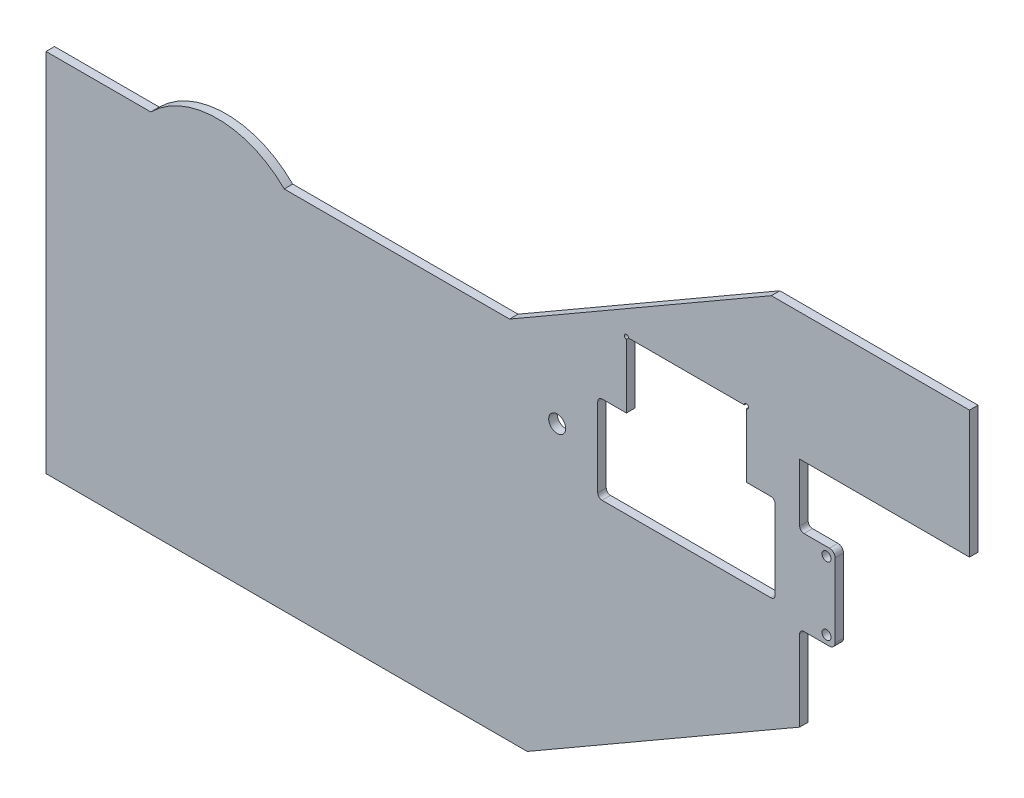
SolidWorks part; units mm, degrees
material "Thornel Mat VMA"
ref_plane "Front Plane" through (0, 0, 0) normal (0, 0, 1) x (1, 0, 0)
ref_plane "Top Plane" through (0, 0, 0) normal (0, 1, 0) x (1, 0, 0)
ref_plane "Right Plane" through (0, 0, 0) normal (1, 0, 0) x (0, 0, -1)
sketch "Sketch1" plane through (0, 0, 0) normal (0, 0, 1) x (1, 0, 0)
  line L1 (-20.4587, 47.6) -> (-183.6375, 47.6)
  line L2 (-20.4587, 47.6) -> (-20.4587, -36.0143)
  line L3 (-20.4587, -36.0143) -> (-183.6375, -36.0143)
  line L4 (-183.6375, 47.6) -> (-183.6375, -36.0143)
extrude "Boss-Extrude1" add sketch "Sketch1" along normal blind 3
sketch "Sketch2" plane through (0, 0, 3) normal (0, 0, 1) x (1, 0, 0)
  circle A0 centre (-24.2887, 24) radius 3
  dimension "D1" = 6
extrude "Cut-Extrude1" cut sketch "Sketch2" against normal blind 70
sketch "Sketch3" plane through (0, 0, 3) normal (0, 0, 1) x (1, 0, 0)
  line L4 (-20.4587, -36.0143) -> (-20.4587, 47.6)
  line L5 (-20.4587, 47.6) -> (-183.6375, 47.6)
  line L6 (-183.6375, 47.6) -> (-183.6375, -36.0143)
  line L7 (-183.6375, -36.0143) -> (-20.4587, -36.0143)
  line L8 (-20.4587, -36.0143) -> (-20.4587, 47.6)
  line L9 (-20.4587, 47.6) -> (-41.1202, 47.6)
  line L10 (-183.6375, 47.6) -> (-183.6375, -36.0143)
  line L11 (-183.6375, -36.0143) -> (-20.4587, -36.0143)
  line L13 (51.3713, 101) -> (-41.1202, 47.6)
  line L14 (-41.1202, 47.6) -> (-120.7247, 47.6)
  line L15 (-204.873, 47.6) -> (-204.873, -81.5667)
  line L16 (-204.873, -81.5667) -> (-34.873, -81.5667)
  line L17 (-34.873, -81.5667) -> (61.3713, -26)
  line L18 (61.3713, -26) -> (61.3713, 2.5)
  line L19 (62.8713, 4) -> (71.8713, 4)
  line L20 (73.8713, 6) -> (73.8713, 32)
  line L21 (71.8713, 34) -> (62.8713, 34)
  line L22 (61.3713, 35.5) -> (61.3713, 56)
  line L23 (61.3713, 56) -> (121.3713, 56)
  line L24 (121.3713, 56) -> (121.3713, 101)
  line L25 (121.3713, 101) -> (51.3713, 101)
  line L26 (51.3713, 101) -> (-41.1202, 47.6)
  line L27 (-167.8527, 47.6) -> (-120.7247, 47.6)
  line L28 (-204.873, 47.6) -> (-204.873, -81.5667)
  line L29 (-204.873, -81.5667) -> (-34.873, -81.5667)
  line L30 (-34.873, -81.5667) -> (61.3713, -26)
  line L31 (61.3713, -26) -> (61.3713, 2.5)
  line L32 (62.8713, 4) -> (71.8713, 4)
  line L33 (73.8713, 6) -> (73.8713, 32)
  line L34 (71.8713, 34) -> (62.8713, 34)
  line L35 (61.3713, 35.5) -> (61.3713, 56)
  line L36 (61.3713, 56) -> (121.3713, 56)
  line L37 (121.3713, 56) -> (121.3713, 101)
  line L38 (121.3713, 101) -> (51.3713, 101)
  line L265 (-167.8527, 47.6) -> (-204.873, 47.6)
  line L266 (-183.6375, 47.6) -> (-204.873, 47.6)
  circle A0 centre (70.8713, 31) radius 1.6 construction
  circle A1 centre (70.8713, 7) radius 1.6 construction
  arc A2 (71.8713, 4) -> (73.8713, 6) centre (71.8713, 6) ccw
  arc A3 (73.8713, 32) -> (71.8713, 34) centre (71.8713, 32) ccw
  arc A4 (71.8713, 4) -> (73.8713, 6) centre (71.8713, 6) ccw
  arc A5 (73.8713, 32) -> (71.8713, 34) centre (71.8713, 32) ccw
  circle A6 centre (70.8713, 31) radius 1.6
  circle A7 centre (70.8713, 7) radius 1.6
  arc A38 (62.8713, 4) -> (61.3713, 2.5) centre (62.8713, 2.5) ccw
  arc A39 (62.8713, 4) -> (61.3713, 2.5) centre (62.8713, 2.5) ccw
  arc A40 (61.3713, 35.5) -> (62.8713, 34) centre (62.8713, 35.5) ccw
  arc A41 (61.3713, 35.5) -> (62.8713, 34) centre (62.8713, 35.5) ccw
  arc A60 (-120.7247, 47.6) -> (-167.8527, 47.6) centre (-144.2887, 24) ccw
  arc A61 (-120.7247, 47.6) -> (-167.8527, 47.6) centre (-144.2887, 24) ccw
  dimension "D1" = 0
  dimension "D2" = 0
extrude "Boss-Extrude2" add sketch "Sketch3" against normal blind 3
sketch "Sketch4" plane through (0, 0, 3) normal (0, 0, 1) x (1, 0, 0)
  line L0 (0.1713, 62.05) -> (0.1713, 39.5) construction
  line L2 (-9.9587, 10) -> (-9.9587, 38) construction
  line L3 (-8.4587, 8.5) -> (51.2013, 8.5) construction
  line L4 (52.7013, 10) -> (52.7013, 38) construction
  line L7 (41.8213, 62.8) -> (0.9213, 62.8) construction
  line L8 (0.1713, 62.05) -> (0.1713, 39.5)
  line L9 (-8.4587, 39.5) -> (0.1713, 39.5)
  line L10 (-9.9587, 10) -> (-9.9587, 38)
  line L11 (-8.4587, 8.5) -> (51.2013, 8.5)
  line L12 (52.7013, 10) -> (52.7013, 38)
  line L13 (42.5713, 39.5) -> (51.2013, 39.5)
  line L14 (42.5713, 62.05) -> (42.5713, 39.5)
  line L15 (41.8213, 62.8) -> (0.9213, 62.8)
  arc A1 (-8.4587, 39.5) -> (-9.9587, 38) centre (-8.4587, 38) ccw construction
  arc A2 (-9.9587, 10) -> (-8.4587, 8.5) centre (-8.4587, 10) ccw construction
  arc A3 (51.2013, 8.5) -> (52.7013, 10) centre (51.2013, 10) ccw construction
  arc A4 (52.7013, 38) -> (51.2013, 39.5) centre (51.2013, 38) ccw construction
  arc A5 (42.5713, 62.05) -> (41.8213, 62.8) centre (42.5713, 62.8) ccw construction
  arc A6 (0.9213, 62.8) -> (0.1713, 62.05) centre (0.1713, 62.8) ccw
  arc A7 (-8.4587, 39.5) -> (-9.9587, 38) centre (-8.4587, 38) ccw
  arc A8 (-9.9587, 10) -> (-8.4587, 8.5) centre (-8.4587, 10) ccw
  arc A9 (51.2013, 8.5) -> (52.7013, 10) centre (51.2013, 10) ccw
  arc A10 (52.7013, 38) -> (51.2013, 39.5) centre (51.2013, 38) ccw
  arc A11 (42.5713, 62.05) -> (41.8213, 62.8) centre (42.5713, 62.8) ccw
extrude "Cut-Extrude2" cut sketch "Sketch4" against normal blind 10
